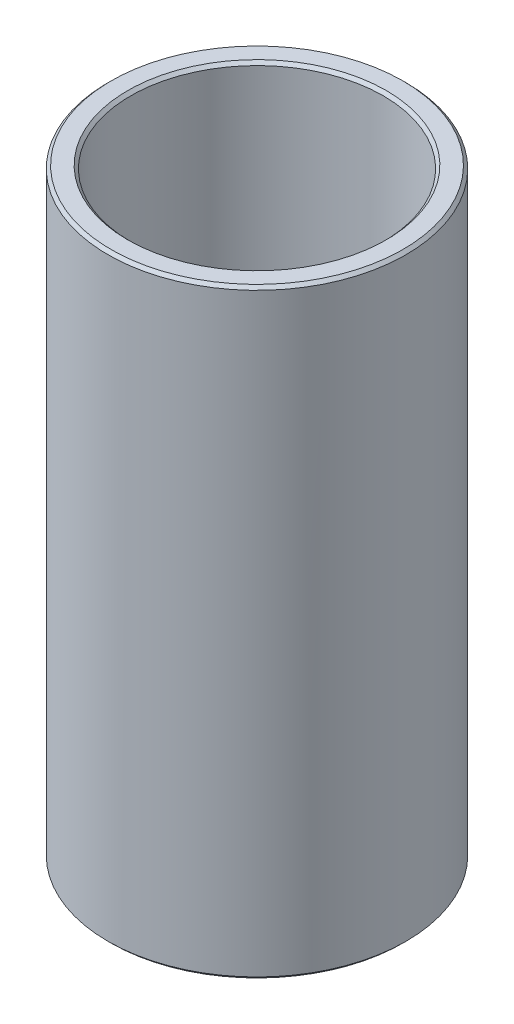
SolidWorks part; units mm, degrees
ref_plane "Front Plane" through (0, 0, 0) normal (0, 0, 1) x (1, 0, 0)
ref_plane "Top Plane" through (0, 0, 0) normal (0, 1, 0) x (1, 0, 0)
ref_plane "Right Plane" through (0, 0, 0) normal (1, 0, 0) x (0, 0, -1)
sketch "Sketch1" plane through (0, 0, 0) normal (0, 1, 0) x (1, 0, 0)
  circle A0 centre (0, 0) radius 55
  dimension "SLEEVE_OD" = 110
extrude "Boss-Extrude1" add sketch "Sketch1" along normal blind 221.6973
sketch "Sketch2" plane through (0, 0, 0) normal (0, 1, 0) x (1, 0, 0)
  circle A0 centre (0, 0) radius 46.615
  dimension "BORE_D" = 93.2301
extrude "Cut-Extrude1" cut sketch "Sketch2" along normal through all
chamfer "Chamfer1" distance 1.1171 angle 45 4 edges at (0, 221.6973, 46.615) (0, 0, 46.615) (0, 0, 55) (0, 221.6973, 55)
